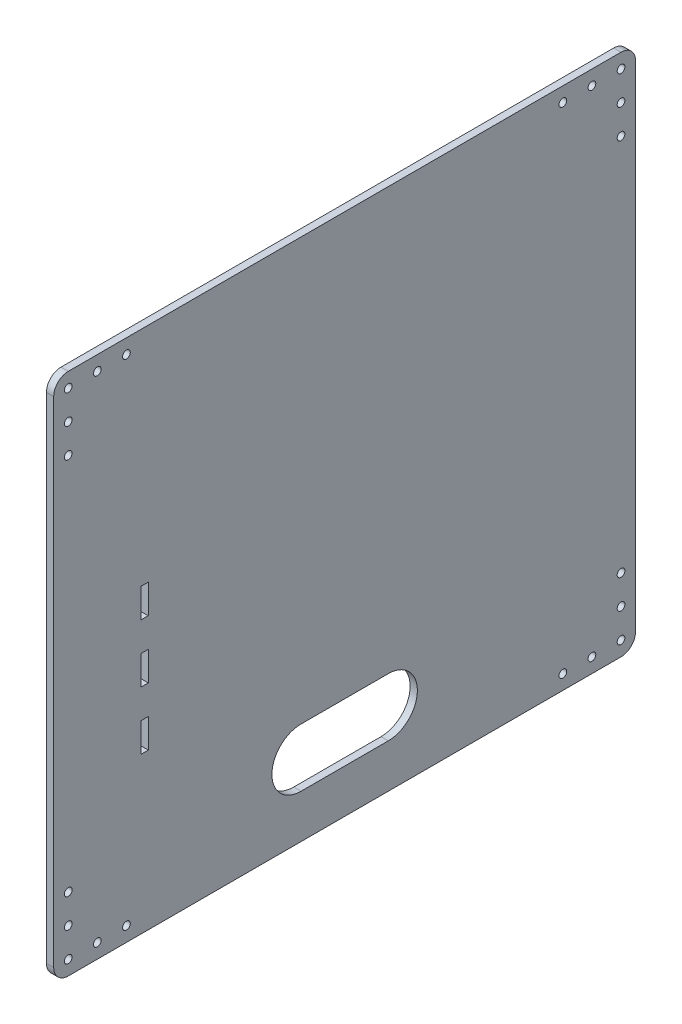
SolidWorks part; units mm, degrees
material "Acrílico (médio-alto impacto)"
ref_plane "Plano frontal" through (0, 0, 0) normal (0, 0, 1) x (1, 0, 0)
ref_plane "Plano superior" through (0, 0, 0) normal (0, 1, 0) x (1, 0, 0)
ref_plane "Plano direito" through (0, 0, 0) normal (1, 0, 0) x (0, 0, -1)
sketch "Esboço1" plane through (0, 0, 0) normal (1, 0, 0) x (0, 0, -1)
  line L1 (-200, 180) -> (200, 180)
  line L2 (-200, 180) -> (-200, -180)
  line L3 (-200, -180) -> (200, -180)
  line L4 (200, 180) -> (200, -180)
  line L5 (-200, 180) -> (200, -180) construction
  line L6 (-200, -180) -> (200, 180) construction
  point P0 (0, 0)
  dimension "D1" = 400
  dimension "D2" = 360
extrude "Ressalto-extrusão1" add sketch "Esboço1" along normal mid plane 5
fillet "Filete1" radius 10 4 edges at (0, 180, -200) (0, -180, -200) (0, -180, 200) (0, 180, 200)
sketch "Esboço2" plane through (2.5, 0, 0) normal (1, 0, 0) x (0, 0, -1)
  line L0 (-200, 170) -> (-200, -170) construction
  line L1 (-190, -180) -> (190, -180) construction
  circle A0 centre (-190, -170) radius 2.65
  circle A1 centre (-170, -170) radius 2.65
  circle A2 centre (-150, -170) radius 2.65
  circle A3 centre (-190, -150) radius 2.65
  circle A4 centre (-190, -130) radius 2.65
  dimension "D1" = 5.3
  dimension "D2" = 10
  dimension "D3" = 10
  dimension "D4" = 3
  dimension "D5" = 3
extrude "Corte-extrusão1" cut sketch "Esboço2" against normal through all
ref_axis "Eixo3" [suppressed] through (-3.3, 0, 0) along (1, 0, 0)
mirror "Espelhar1" about plane through (0, 0, 0) normal (0, 0, 1) of "Corte-extrusão1"
mirror "Espelhar2" about plane through (0, 0, 0) normal (0, 1, 0) of "Espelhar1"
sketch "Esboço3" plane through (2.5, 0, 0) normal (1, 0, 0) x (0, 0, -1)
  line L1 (-135, -53) -> (-140, -53)
  line L2 (-135, -53) -> (-135, -73)
  line L3 (-135, -73) -> (-140, -73)
  line L4 (-140, -53) -> (-140, -73)
  line L6 (-200, 170) -> (-200, -170) construction
  line L7 (-190, -180) -> (190, -180) construction
  dimension "D1" = 5
  dimension "D2" = 20
  dimension "D3" = 60
  dimension "D4" = 107
extrude "Corte-extrusão2" cut sketch "Esboço3" against normal through all
pattern_linear "Padrão linear1" count 3 spacing 40 along (0, 1, 0) of "Corte-extrusão2"
sketch "Esboço4" plane through (-2.5, 0, 0) normal (-1, 0, 0) x (0, 0, 1)
  line L0 (200, 0) -> (-200, 0) construction
  line L1 (200, 170) -> (200, -170) construction
  line L2 (-200, -170) -> (-200, 170) construction
  line L3 (0, -180) -> (0, 180) construction
  line L4 (190, -180) -> (-190, -180) construction
  line L5 (-190, 180) -> (190, 180) construction
  line L6 (200, -130) -> (-200, -130) construction
  line L7 (30, -130) -> (-30, -130) construction
  line L8 (30, -150) -> (-30, -150)
  line L9 (30, -110) -> (-30, -110)
  arc A0 (30, -150) -> (30, -110) centre (30, -130) ccw
  arc A1 (-30, -110) -> (-30, -150) centre (-30, -130) ccw
  point P16 (0, -130)
  dimension "D1" = 130
  dimension "D2" = 40
  dimension "D3" = 60
extrude "Corte-extrusão3" cut sketch "Esboço4" against normal through all
